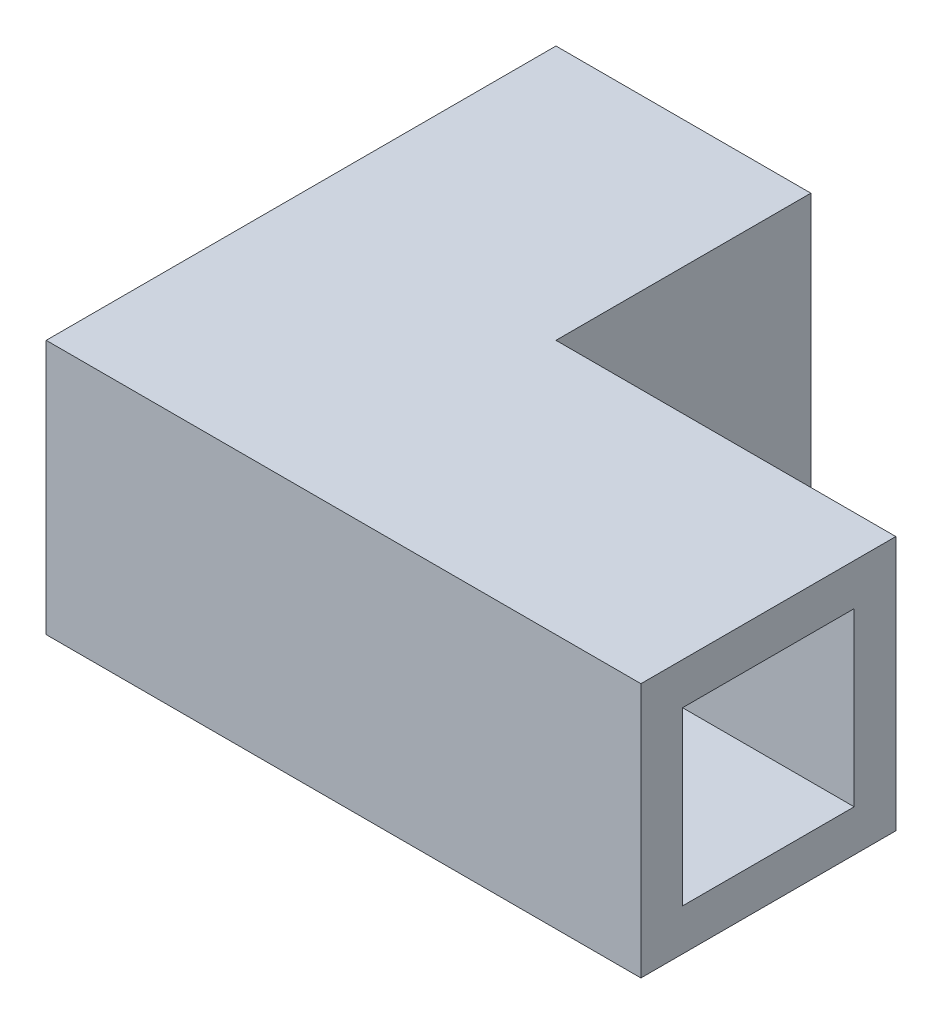
SolidWorks part; units mm, degrees
ref_plane "Спереди" through (0, 0, 0) normal (0, 0, 1) x (1, 0, 0)
ref_plane "Сверху" through (0, 0, 0) normal (0, 1, 0) x (1, 0, 0)
ref_plane "Справа" through (0, 0, 0) normal (1, 0, 0) x (0, 0, -1)
sketch "Sketch1" plane through (0, 0, 0) normal (0, 1, 0) x (1, 0, 0)
  line L0 (-20, 15) -> (-20, 0) construction
  line L1 (0, 0) -> (20, 0)
  line L2 (20, 0) -> (20, 15)
  line L3 (20, 15) -> (0, 15)
  line L4 (0, 15) -> (-20, 15) construction
  line L5 (-20, 0) -> (0, 0) construction
  line L6 (0, 0) -> (0, 15) construction
  line L7 (0, 15) -> (0, 30)
  line L8 (0, 30) -> (-15, 30)
  line L9 (-15, 30) -> (-15, 0)
  line L10 (-15, 0) -> (0, 0)
  dimension "D1" = 180
  dimension "D2" = 15
  dimension "D3" = 20
  dimension "D4" = 15
  dimension "D5" = 30
extrude "Boss-Extrude1" add sketch "Sketch1" along normal blind 15
sketch "Sketch2" plane through (20, 0, 0) normal (1, 0, 0) x (0, 0, -1)
  line L0 (15, 7.5) -> (0, 7.5) construction
  line L1 (15, 15) -> (15, 0) construction
  line L2 (0, 15) -> (0, 0) construction
  line L4 (2.45, 2.45) -> (12.55, 2.45)
  line L5 (2.45, 2.45) -> (2.45, 12.55)
  line L6 (2.45, 12.55) -> (12.55, 12.55)
  line L7 (12.55, 2.45) -> (12.55, 12.55)
  line L8 (2.45, 2.45) -> (12.55, 12.55) construction
  line L9 (2.45, 12.55) -> (12.55, 2.45) construction
  point P6 (7.5, 7.5)
  dimension "D1" = 10.1
extrude "Cut-Extrude1" cut sketch "Sketch2" against normal blind 20
sketch "Sketch3" plane through (0, 0, -30) normal (0, 0, -1) x (-1, 0, 0)
  line L0 (15, 7.5) -> (0, 7.5) construction
  line L1 (15, 15) -> (15, 0) construction
  line L2 (0, 15) -> (0, 0) construction
  line L4 (2.45, 12.55) -> (12.55, 12.55)
  line L5 (2.45, 12.55) -> (2.45, 2.45)
  line L6 (2.45, 2.45) -> (12.55, 2.45)
  line L7 (12.55, 12.55) -> (12.55, 2.45)
  line L8 (2.45, 12.55) -> (12.55, 2.45) construction
  line L9 (2.45, 2.45) -> (12.55, 12.55) construction
  point P6 (7.5, 7.5)
  dimension "D1" = 10.1
extrude "Cut-Extrude2" cut sketch "Sketch3" against normal blind 17
sketch "Sketch4" plane through (0, 0, -13) normal (0, 0, -1) x (-1, 0, 0)
  line L0 (2.45, 2.45) -> (12.55, 12.55) construction
  line L2 (11.5, 11.5) -> (3.5, 11.5)
  line L3 (11.5, 11.5) -> (11.5, 3.5)
  line L4 (11.5, 3.5) -> (3.5, 3.5)
  line L5 (3.5, 11.5) -> (3.5, 3.5)
  line L6 (11.5, 11.5) -> (3.5, 3.5) construction
  line L7 (11.5, 3.5) -> (3.5, 11.5) construction
  point P4 (7.5, 7.5)
  dimension "D1" = 8
extrude "Cut-Extrude3" cut sketch "Sketch4" against normal blind 4
sketch "Sketch5" plane through (0, 0, 0) normal (1, 0, 0) x (0, 0, -1)
  line L0 (12.55, 12.55) -> (2.45, 2.45) construction
  line L2 (11.5, 11.5) -> (3.5, 11.5)
  line L3 (11.5, 11.5) -> (11.5, 3.5)
  line L4 (11.5, 3.5) -> (3.5, 3.5)
  line L5 (3.5, 11.5) -> (3.5, 3.5)
  line L6 (11.5, 11.5) -> (3.5, 3.5) construction
  line L7 (11.5, 3.5) -> (3.5, 11.5) construction
  point P4 (7.5, 7.5)
  dimension "D1" = 8
extrude "Cut-Extrude4" cut sketch "Sketch5" against normal up to surface (11.5 mm away) up to face at (-11.5, 7.5, -11)
fillet "Fillet1" radius 5 2 edges at (-3.5, 7.5, -11.5) (-11.5, 7.5, -3.5)
